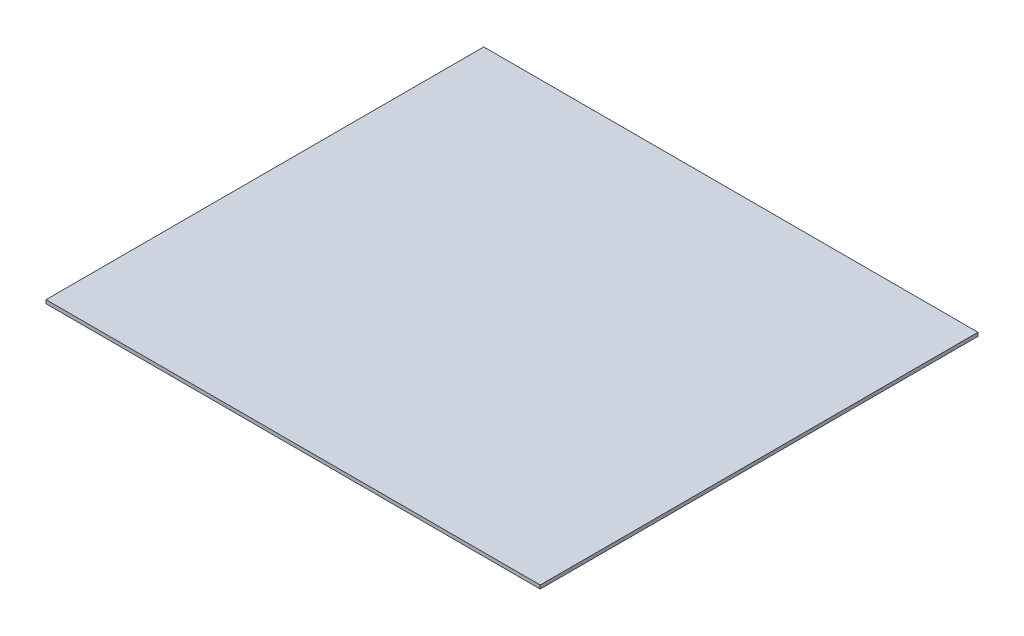
SolidWorks part; units mm, degrees
material "Acrylic (Medium-high impact)"
ref_plane "Front Plane" through (0, 0, 0) normal (0, 0, 1) x (1, 0, 0)
ref_plane "Top Plane" through (0, 0, 0) normal (0, 1, 0) x (1, 0, 0)
ref_plane "Right Plane" through (0, 0, 0) normal (1, 0, 0) x (0, 0, -1)
sketch "Sketch1" plane through (0, 0, 0) normal (0, 1, 0) x (1, 0, 0)
  line L1 (-222.25, -196.85) -> (222.25, -196.85)
  line L2 (-222.25, -196.85) -> (-222.25, 196.85)
  line L3 (-222.25, 196.85) -> (222.25, 196.85)
  line L4 (222.25, -196.85) -> (222.25, 196.85)
  line L5 (-222.25, -196.85) -> (222.25, 196.85) construction
  line L6 (-222.25, 196.85) -> (222.25, -196.85) construction
  point P0 (0, 0)
  dimension "D1" = 393.7
  dimension "D2" = 444.5
extrude "Boss-Extrude1" add sketch "Sketch1" along normal blind 3.175
